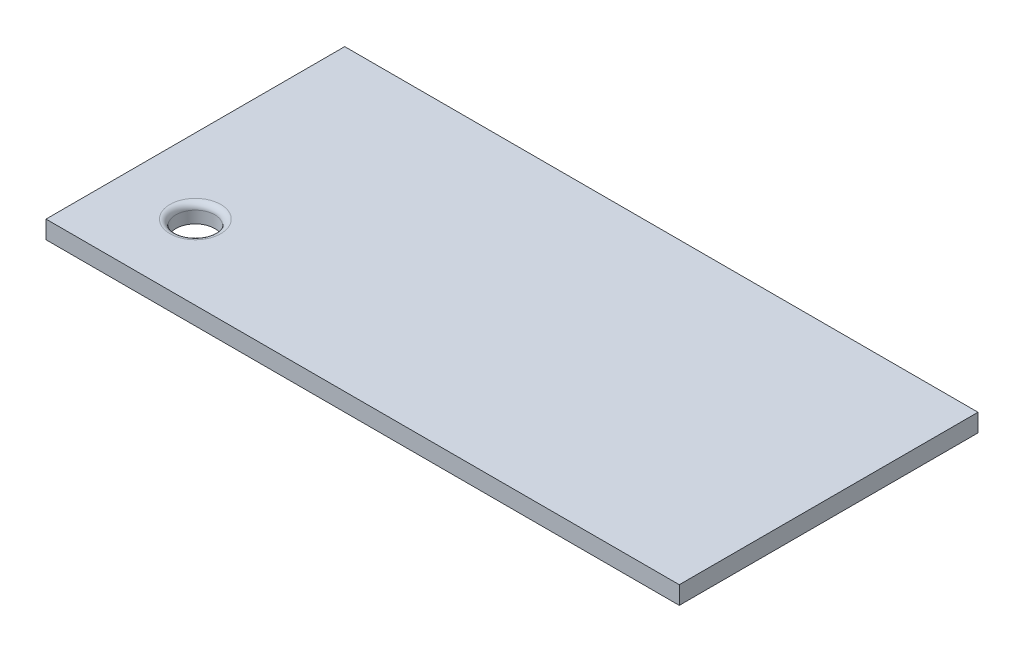
SolidWorks part; units mm, degrees
material "Pine"
ref_plane "Front Plane" through (0, 0, 0) normal (0, 0, 1) x (1, 0, 0)
ref_plane "Top Plane" through (0, 0, 0) normal (0, 1, 0) x (1, 0, 0)
ref_plane "Right Plane" through (0, 0, 0) normal (1, 0, 0) x (0, 0, -1)
sketch "Sketch1" plane through (0, 0, 0) normal (0, 1, 0) x (1, 0, 0)
  line L1 (0, 0) -> (212, 0)
  line L2 (0, 0) -> (0, 100)
  line L3 (0, 100) -> (212, 100)
  line L4 (212, 0) -> (212, 100)
  dimension "D1" = 212
  dimension "D2" = 100
extrude "Boss-Extrude1" add sketch "Sketch1" along normal blind 6
sketch "Sketch2" plane through (0, 6, 0) normal (0, 1, 0) x (1, 0, 0)
  line L0 (0, 100) -> (0, 0) construction
  line L1 (0, 0) -> (212, 0) construction
  circle A0 centre (25, 25) radius 6.5
  dimension "D1" = 13
  dimension "D2" = 25
  dimension "D3" = 25
extrude "Cut-Extrude1" cut sketch "Sketch2" against normal through all
fillet "Fillet1" radius 2 1 edges at (25, 6, -18.5)
equation "\"BoardThickness\"= 6"
equation "\"D1@Boss-Extrude1\"=\"BoardThickness\""
equation "\"D1@Sketch1\"=200+\"BoardThickness\"*2"
